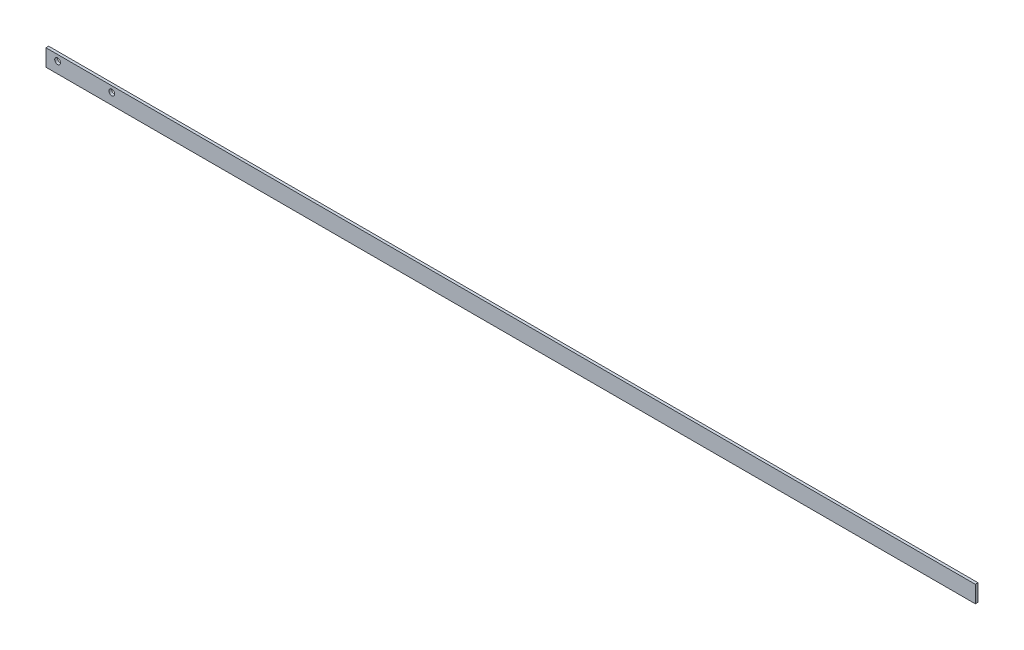
SolidWorks part; units mm, degrees
ref_plane "Front Plane" through (0, 0, 0) normal (0, 0, 1) x (1, 0, 0)
ref_plane "Top Plane" through (0, 0, 0) normal (0, 1, 0) x (1, 0, 0)
ref_plane "Right Plane" through (0, 0, 0) normal (1, 0, 0) x (0, 0, -1)
sketch "Sketch1" plane through (0, 0, 0) normal (0, 0, 1) x (1, 0, 0)
  line L1 (-304.8, -5.5499) -> (304.8, -5.5499)
  line L2 (-304.8, -5.5499) -> (-304.8, 5.5499)
  line L3 (-304.8, 5.5499) -> (304.8, 5.5499)
  line L4 (304.8, -5.5499) -> (304.8, 5.5499)
  line L5 (-304.8, -5.5499) -> (304.8, 5.5499) construction
  line L6 (-304.8, 5.5499) -> (304.8, -5.5499) construction
  point P0 (0, 0)
  dimension "D1" = 609.6
  dimension "D2" = 11.0998
extrude "Boss-Extrude1" add sketch "Sketch1" along normal mid plane 1.778
sketch "Sketch2" plane through (0, 0, 0.889) normal (0, 0, 1) x (1, 0, 0)
  line L0 (304.8, 5.5499) -> (-304.8, 5.5499) construction
  line L1 (-304.8, 5.5499) -> (-304.8, -5.5499) construction
  circle A0 centre (-297.18, 1.7399) radius 1.651
  circle A1 centre (-261.62, 1.7399) radius 1.651
  dimension "D2" = 3.302
  dimension "D1" = 3.81
  dimension "D3" = 7.62
  dimension "D4" = 35.56
hole_wizard "#6 Clearance Hole1" positions "Sketch3" profile "Sketch4" hole size "#6" standard "ANSI Inch" end condition through all
sketch "Sketch3" plane through (0, 0, 0.889) normal (0, 0, 1) x (1, 0, 0)
  point P0 (-297.18, 1.7399)
  point P3 (-261.62, 1.7399)
sketch "Sketch4" plane through (-297.18, 1.7399, 0.889) normal (1, 0, 0) x (0, -1, 0)
  line L0 (0, 0) -> (0, 1.778)
  line L1 (0, 1.778) -> (1.8986, 1.778)
  line L2 (1.8986, 1.778) -> (1.8986, 0)
  line L5 (1.8986, 0) -> (0, 0)
  line L11 (0, -6.35) -> (0, 107.95) construction
  dimension "Thru Hole Dia." = 3.7973
  dimension "Thru Hole Depth" = 1.778
